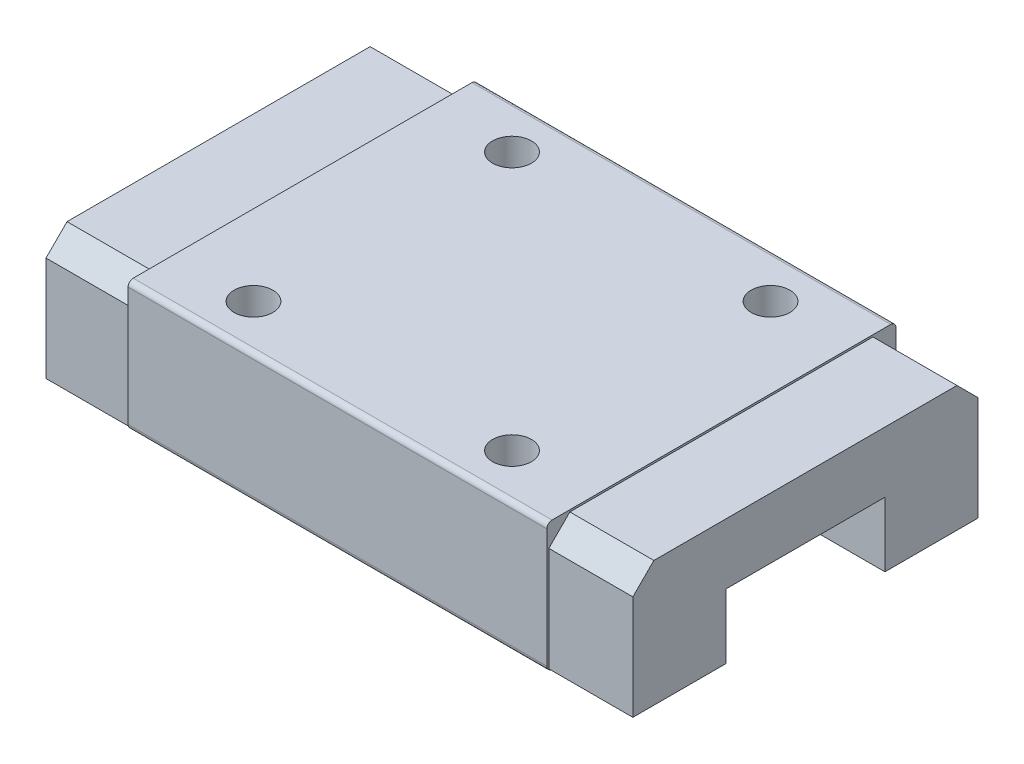
SolidWorks part; units mm, degrees
ref_plane "Front Plane" through (0, 0, 0) normal (0, 0, 1) x (1, 0, 0)
ref_plane "Top Plane" through (0, 0, 0) normal (0, 1, 0) x (1, 0, 0)
ref_plane "Right Plane" through (0, 0, 0) normal (1, 0, 0) x (0, 0, -1)
sketch "Sketch1" plane through (0, 0, 0) normal (1, 0, 0) x (0, 0, -1)
  line L0 (0, -3.307) -> (0, 0) construction
  line L1 (13.5, 0) -> (-13.5, 0)
  line L2 (-13.5, 0) -> (-13.5, -10)
  line L3 (-13.5, -10) -> (-6, -10)
  line L4 (-6, -10) -> (-6, -5)
  line L5 (-6, -5) -> (6, -5)
  line L6 (13.5, 0) -> (13.5, -10)
  line L7 (13.5, -10) -> (6, -10)
  line L8 (6, -10) -> (6, -5)
  point P12 (0, -5)
  dimension "D1" = 27
  dimension "D2" = 10
  dimension "D3" = 5
  dimension "D4" = 7.5
  dimension "D5" = 12
extrude "Boss-Extrude1" add sketch "Sketch1" along normal blind 16.2 and the other way blind 16.2
sketch "Sketch2" plane through (0, 0, 0) normal (0, 1, 0) x (1, 0, 0)
  line L0 (0, -3.1479) -> (0, 0) construction
  line L1 (0, 0) -> (-3.5449, 0) construction
  circle A0 centre (-10, 10) radius 1.5
  circle A1 centre (-10, -10) radius 1.5
  circle A2 centre (10, -10) radius 1.5
  circle A3 centre (10, 10) radius 1.5
  dimension "D1" = 20
  dimension "D2" = 20
  dimension "D3" = 3
extrude "Cut-Extrude1" cut sketch "Sketch2" against normal blind 5
sketch "Sketch3" plane through (-16.2, 0, 0) normal (-1, 0, 0) x (0, 0, 1)
  line L8 (-13.35, -1.7763) -> (-11.7237, -0.15)
  line L9 (0, -2.5386) -> (0, 0) construction
  line L10 (13.35, -1.7763) -> (11.7237, -0.15)
  line L16 (13.35, -9.85) -> (13.35, -0.15)
  line L17 (6.15, -9.85) -> (13.35, -9.85)
  line L18 (6.15, -4.85) -> (6.15, -9.85)
  line L19 (-6.15, -4.85) -> (6.15, -4.85)
  line L20 (-6.15, -9.85) -> (-6.15, -4.85)
  line L21 (-13.35, -9.85) -> (-6.15, -9.85)
  line L22 (-13.35, -0.15) -> (-13.35, -9.85)
  line L23 (13.35, -0.15) -> (-13.35, -0.15)
  line L24 (13.35, -9.85) -> (13.35, -1.7763)
  line L25 (6.15, -9.85) -> (13.35, -9.85)
  line L26 (6.15, -4.85) -> (6.15, -9.85)
  line L27 (-6.15, -4.85) -> (6.15, -4.85)
  line L28 (-6.15, -9.85) -> (-6.15, -4.85)
  line L29 (-13.35, -9.85) -> (-6.15, -9.85)
  line L30 (-13.35, -1.7763) -> (-13.35, -9.85)
  line L31 (11.7237, -0.15) -> (-11.7237, -0.15)
  dimension "D2" = 2.3
  dimension "D3" = 45
  dimension "D1" = 0.15
extrude "Boss-Extrude2" add sketch "Sketch3" along normal blind 6.5 separate body
sketch "Sketch4" plane through (16.2, 0, 0) normal (1, 0, 0) x (0, 0, -1)
  line L10 (13.35, -1.7763) -> (11.7237, -0.15)
  line L11 (11.7237, -0.15) -> (-11.7237, -0.15)
  line L12 (-11.7237, -0.15) -> (-13.35, -1.7763)
  line L13 (-13.35, -1.7763) -> (-13.35, -9.85)
  line L14 (-13.35, -9.85) -> (-6.15, -9.85)
  line L15 (-6.15, -9.85) -> (-6.15, -4.85)
  line L16 (-6.15, -4.85) -> (6.15, -4.85)
  line L17 (6.15, -4.85) -> (6.15, -9.85)
  line L18 (6.15, -9.85) -> (13.35, -9.85)
  line L19 (13.35, -9.85) -> (13.35, -1.7763)
  line L20 (13.35, -1.7763) -> (11.7237, -0.15)
  line L21 (11.7237, -0.15) -> (-11.7237, -0.15)
  line L22 (-11.7237, -0.15) -> (-13.35, -1.7763)
  line L23 (-13.35, -1.7763) -> (-13.35, -9.85)
  line L24 (-13.35, -9.85) -> (-6.15, -9.85)
  line L25 (-6.15, -9.85) -> (-6.15, -4.85)
  line L26 (-6.15, -4.85) -> (6.15, -4.85)
  line L27 (6.15, -4.85) -> (6.15, -9.85)
  line L28 (6.15, -9.85) -> (13.35, -9.85)
  line L29 (13.35, -9.85) -> (13.35, -1.7763)
  dimension "D1" = 0
extrude "Boss-Extrude3" add sketch "Sketch4" along normal blind 6.5 separate body
fillet "Fillet1" radius 0.4 4 edges at (0, -10, -13.5) (0, 0, -13.5) (0, -10, 13.5) (0, 0, 13.5)
